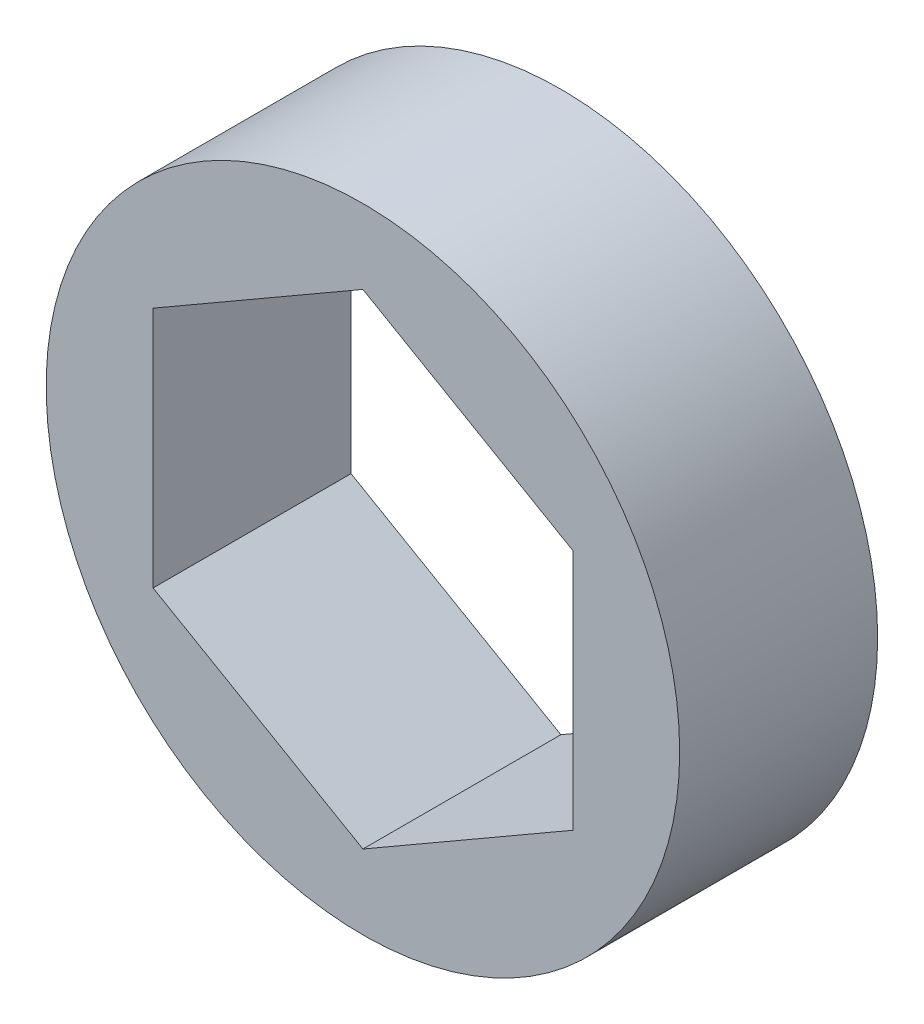
SolidWorks part; units mm, degrees
material "Nylon 101"
ref_plane "Front Plane" through (0, 0, 0) normal (0, 0, 1) x (1, 0, 0)
ref_plane "Top Plane" through (0, 0, 0) normal (0, 1, 0) x (1, 0, 0)
ref_plane "Right Plane" through (0, 0, 0) normal (1, 0, 0) x (0, 0, -1)
sketch "Sketch1" plane through (0, 0, 0) normal (0, 0, 1) x (1, 0, 0)
  line L1 (0, 7.7723) -> (-6.731, 3.8861)
  line L2 (-6.731, 3.8861) -> (-6.731, -3.8861)
  line L3 (-6.731, -3.8861) -> (0, -7.7723)
  line L4 (0, -7.7723) -> (6.731, -3.8861)
  line L5 (6.731, -3.8861) -> (6.731, 3.8861)
  line L6 (6.731, 3.8861) -> (0, 7.7723)
  circle A0 centre (0, 0) radius 10.16
  circle A1 centre (0, 0) radius 6.731 construction
  point P3 (0, 0)
  dimension "D1" = 13.462
  dimension "D2" = 20.32
extrude "Boss-Extrude1" add sketch "Sketch1" along normal mid plane 6.35
